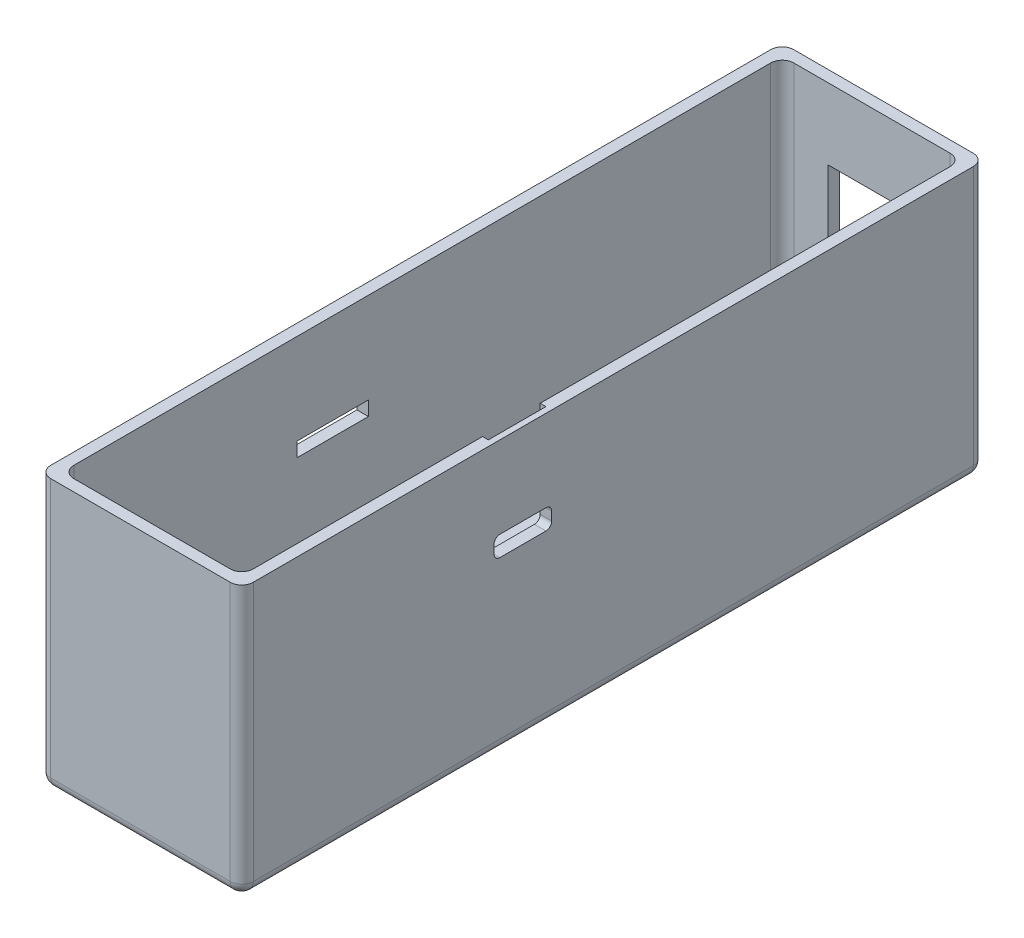
SolidWorks part; units mm, degrees
ref_plane "Plan de face" through (0, 0, 0) normal (0, 0, 1) x (1, 0, 0)
ref_plane "Plan de dessus" through (0, 0, 0) normal (0, 1, 0) x (1, 0, 0)
ref_plane "Plan de droite" through (0, 0, 0) normal (1, 0, 0) x (0, 0, -1)
sketch "Sketch1" plane through (0, 0, 0) normal (0, 1, 0) x (1, 0, 0)
  line L1 (-15.58, -62.5) -> (15.58, -62.5)
  line L2 (-15.58, -62.5) -> (-15.58, 62.5)
  line L3 (-15.58, 62.5) -> (15.58, 62.5)
  line L4 (15.58, -62.5) -> (15.58, 62.5)
  line L5 (-15.58, -62.5) -> (15.58, 62.5) construction
  line L6 (-15.58, 62.5) -> (15.58, -62.5) construction
  point P0 (0, 0)
  dimension "D1" = 31.16
  dimension "D2" = 125
extrude "Boss-Extrude1" add sketch "Sketch1" along normal blind 45
shell "Shell1" thickness 2 removed face at (0, 45, 0) outward yes
fillet "Fillet1" radius 2 12 edges at (-15.58, 22.5, -62.5) (-15.58, 22.5, 62.5) (15.58, 22.5, 62.5) (15.58, 22.5, -62.5) (17.58, 21.5, -64.5) (17.58, -2, 0) (0, -2, 64.5) (17.58, 21.5, 64.5) (-17.58, 21.5, 64.5) (0, -2, -64.5) (-17.58, 21.5, -64.5) (-17.58, -2, 0)
sketch "Sketch3" plane through (0, 0, -64.5) normal (0, 0, -1) x (-1, 0, 0)
  line L0 (-15.58, 45) -> (15.58, 0) construction
  line L1 (-15.58, 45) -> (-15.58, 0) construction
  line L2 (-15.58, 45) -> (15.58, 45) construction
  line L4 (-7.64, 12.35) -> (7.64, 12.35)
  line L5 (-7.64, 12.35) -> (-7.64, 32.65)
  line L6 (-7.64, 32.65) -> (7.64, 32.65)
  line L7 (7.64, 12.35) -> (7.64, 32.65)
  line L8 (-7.64, 12.35) -> (7.64, 32.65) construction
  line L9 (-7.64, 32.65) -> (7.64, 12.35) construction
  point P7 (0, 22.5)
  dimension "D1" = 15.28
  dimension "D2" = 20.3
extrude "Cut-Extrude2" cut sketch "Sketch3" against normal blind 10
sketch "Sketch4" plane through (17.58, 0, 0) normal (1, 0, 0) x (0, 0, -1)
  line L0 (-62.5, 45) -> (-62.5, 0) construction
  line L1 (-20.69, 30.8) -> (-10.69, 30.8)
  line L2 (-20.69, 30.8) -> (-20.69, 27.3)
  line L3 (-20.69, 27.3) -> (-10.69, 27.3)
  line L4 (-10.69, 30.8) -> (-10.69, 27.3)
  line L5 (-20.69, 30.8) -> (-10.69, 27.3) construction
  line L6 (-20.69, 27.3) -> (-10.69, 30.8) construction
  line L8 (-62.5, 0) -> (62.5, 0) construction
  line L9 (-62.5, 5.3289) -> (-53, 5.3289) construction
  point P0 (-15.69, 29.05)
  point P5 (0, 0)
  dimension "D5" = 9.5
  dimension "D1" = 10
  dimension "D2" = 3.5
  dimension "D4" = 27.3
  dimension "D3" = 37.31
extrude "Cut-Extrude3" cut sketch "Sketch4" against normal blind 6.5
sketch "Sketch5" plane through (-17.58, 0, 0) normal (-1, 0, 0) x (0, 0, 1)
  line L0 (62.5, 0) -> (62.5, 45) construction
  line L1 (21.75, 26.76) -> (9.35, 26.76)
  line L2 (21.75, 26.76) -> (21.75, 29.26)
  line L3 (21.75, 29.26) -> (9.35, 29.26)
  line L4 (9.35, 26.76) -> (9.35, 29.26)
  line L5 (21.75, 26.76) -> (9.35, 29.26) construction
  line L6 (21.75, 29.26) -> (9.35, 26.76) construction
  line L7 (-62.5, 0) -> (62.5, 0) construction
  line L8 (62.5, 3.2142) -> (53, 3.2142) construction
  point P0 (15.55, 28.01)
  dimension "D1" = 12.4
  dimension "D2" = 2.5
  dimension "D4" = 26.76
  dimension "D5" = 9.5
  dimension "D3" = 37.45
extrude "Cut-Extrude4" cut sketch "Sketch5" against normal blind 6.5
fillet "Fillet3" radius 1 4 edges at (16.58, 30.8, 20.69) (16.58, 27.3, 20.69) (16.58, 27.3, 10.69) (16.58, 30.8, 10.69)
sketch "Sketch6" plane through (-11.5843, 0, -32.0372) normal (0, 1, 0) x (0, 0, 1)
  text T0 "GammaTroniques\r\n10/2024" font "Arial" height 5
  point P1 (-24.5874, 15.2064)
  point P2 (8.9769, 14.9649)
  point P3 (0, 0)
  point P4 (0, 0)
  point P5 (0, 0)
extrude "Cut-Extrude5" cut sketch "Sketch6" against normal blind 0.5
sketch "Sketch7" plane through (0, 0, 0) normal (0, 1, 0) x (1, 0, 0)
  line L0 (13.58, 62.5) -> (-13.58, 62.5) construction
  line L1 (15.58, -60.5) -> (15.58, 60.5) construction
  line L2 (-15.58, 60.5) -> (-15.58, -60.5) construction
  line L3 (-15.58, 0) -> (15.58, 0) construction
  line L4 (12.7, 55) -> (15.58, 55)
  line L5 (15.58, -60.5) -> (15.58, 60.5) construction
  line L6 (12.7, 50) -> (15.58, 50)
  line L7 (15.58, 50) -> (15.58, 55)
  line L8 (0, 62.5) -> (0, -62.5) construction
  line L9 (-13.58, -62.5) -> (13.58, -62.5) construction
  line L10 (12.7, -50.5) -> (15.58, -50.5)
  line L11 (15.58, -55.5) -> (15.58, -50.5)
  line L12 (12.7, -55.5) -> (15.58, -55.5)
  line L13 (-12.7, -55.5) -> (-15.58, -55.5)
  line L14 (-12.7, -50.5) -> (-15.58, -50.5)
  line L15 (-12.7, 50) -> (-15.58, 50)
  line L16 (-15.58, 50) -> (-15.58, 55)
  line L17 (-12.7, 55) -> (-15.58, 55)
  line L18 (-15.58, -50.5) -> (-15.58, -55.5)
  circle A0 centre (12.7, 52.5) radius 2.5
  circle A5 centre (12.7, 52.5) radius 1.5
  circle A6 centre (12.7, -53) radius 1.5
  circle A7 centre (12.7, -53) radius 2.5
  circle A8 centre (-12.7, -53) radius 1.5
  circle A9 centre (-12.7, -53) radius 2.5
  circle A10 centre (-12.7, 52.5) radius 2.5
  circle A11 centre (-12.7, 52.5) radius 1.5
  dimension "D1" = 5
  dimension "D2" = 2
  dimension "D3" = 9.5
  dimension "D5" = 2.88
  dimension "D4" = 10
  dimension "D6" = 31.16
extrude "Boss-Extrude2" add sketch "Sketch7" along normal blind 4.5 contours A0 L6 L7 L4 | A0 A5 | L15 A10 L17 L16 | A10 A11 | A7 A6 | A7 L12 L11 L10 | A9 A8 | L13 A9 L14 L18
sketch "Sketch8" plane through (17.58, 0, 0) normal (1, 0, 0) x (0, 0, -1)
  text T0 "SIM" font "Arial" height 3
  point P1 (-26.3915, 33.0119)
sketch "Sketch9" plane through (-17.58, 0, 0) normal (-1, 0, 0) x (0, 0, 1)
  text T0 "SIM\r\n" font "Arial" height 5
  point P1 (9.6142, 18.9696)
  point P2 (0, 0)
  point P3 (9.2286, 18.9696)
extrude "Cut-Extrude6" cut sketch "Sketch9" against normal blind 0.5
sketch "Sketch10" plane through (15.58, 0, 0) normal (-1, 0, 0) x (0, 0, 1)
  line L0 (20.69, 29.8) -> (20.69, 53.6375) construction
  line L2 (10.69, 29.8) -> (20.69, 29.8)
  line L3 (10.69, 29.8) -> (10.69, 53.6375)
  line L4 (10.69, 53.6375) -> (20.69, 53.6375)
  line L5 (20.69, 29.8) -> (20.69, 53.6375)
extrude "Cut-Extrude7" cut sketch "Sketch10" against normal blind 1
equation "\"D1@Sketch1\"=30.66mm+0.5"
equation "\"D4@Sketch5\"=22.26mm+4.5"
equation "\"D4@Sketch4\"=22.80mm+4.5"
